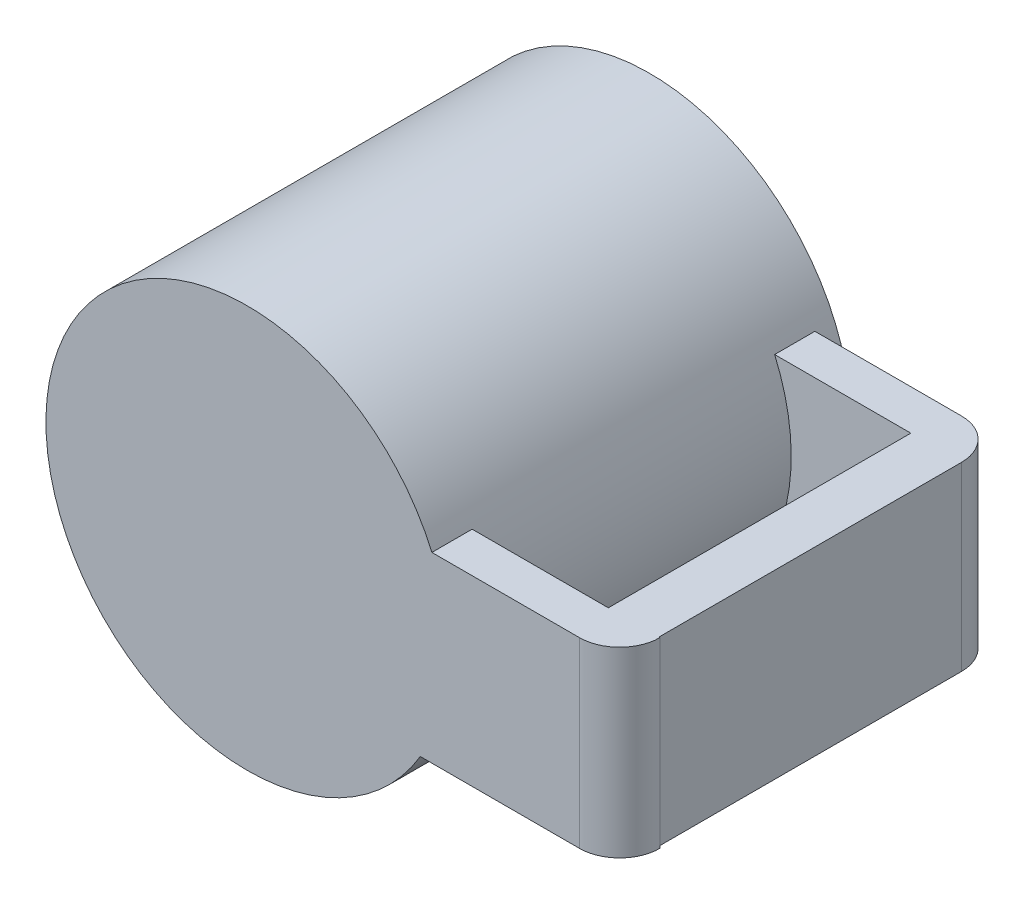
SolidWorks part; units mm, degrees
ref_plane "前基準面" through (0, 0, 0) normal (0, 0, 1) x (1, 0, 0)
ref_plane "上基準面" through (0, 0, 0) normal (0, 1, 0) x (1, 0, 0)
ref_plane "右基準面" through (0, 0, 0) normal (1, 0, 0) x (0, 0, -1)
sketch "草圖1" plane through (0.3827, 0, 0) normal (0, 0, 1) x (1, 0, 0)
  circle A0 centre (-75.5944, 2.55) radius 5
extrude "填料-伸長1" add sketch "草圖1" along normal blind 10 contours A0
ref_plane "平面1" through (0, 0, 9) normal (0, 0, 1) x (1, 0, 0)
sketch "草圖9" plane through (6.1278, 0, 9) normal (0, 0, 1) x (1, 0, 0)
  line L0 (-79.2052, 4.535) -> (-72.0845, 4.535)
  line L1 (-72.0845, 4.535) -> (-72.0845, 0)
  line L2 (-72.0845, 0) -> (-79.2052, 0)
  line L3 (-79.2052, 0) -> (-79.2052, 4.535)
extrude "填料-伸長6" add sketch "草圖9" along normal blind 1
sketch "草圖11" plane through (9.5745, 4.535, 0.4843) normal (0, 1, 0) x (1, 0, 0)
  line L0 (-75.5559, -9) -> (-75.5559, 0)
  line L2 (-75.5559, 0) -> (-76.8136, 0)
  line L3 (-76.8136, 0) -> (-76.8136, -9)
  line L4 (-76.8136, -9) -> (-75.5559, -9)
extrude "填料-伸長7" add sketch "草圖11" against normal blind 4.5 separate body
sketch "草圖12" plane through (-67.2391, 0, 0) normal (-1, 0, 0) x (0, 0, 1)
  line L0 (0.4843, 4.535) -> (0.4843, 0)
  line L1 (0.4843, 4.535) -> (1.4836, 4.535)
  line L2 (1.4836, 4.535) -> (1.4836, 0.035)
  line L3 (0.4843, 0.035) -> (9.4843, 0.035) construction
  line L4 (1.4836, 0.035) -> (0.4843, 0)
extrude "填料-伸長8" add sketch "草圖12" along normal blind 6
fillet "圓角8" radius 1 1 edges at (-65.9814, 2.285, 0.4843)
fillet "圓角9" radius 1 1 edges at (-65.9567, 2.2675, 10)
